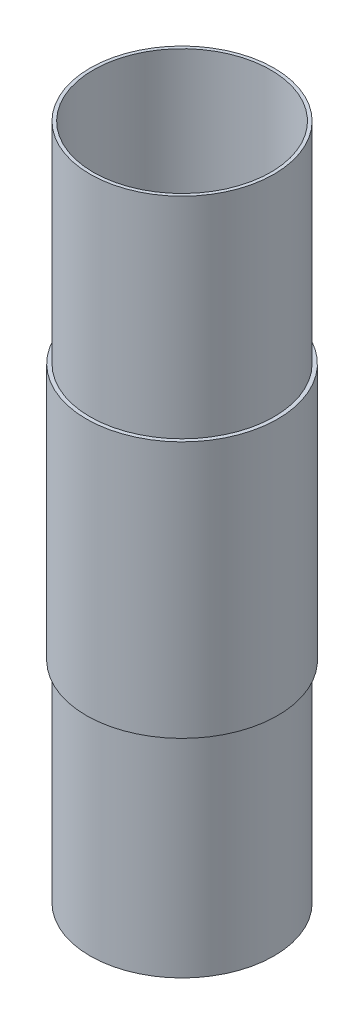
SolidWorks part; units mm, degrees
ref_plane "Front Plane" through (0, 0, 0) normal (0, 0, 1) x (1, 0, 0)
ref_plane "Top Plane" through (0, 0, 0) normal (0, 1, 0) x (1, 0, 0)
ref_plane "Right Plane" through (0, 0, 0) normal (1, 0, 0) x (0, 0, -1)
sketch "Sketch1" plane through (0, 0, 0) normal (0, 1, 0) x (1, 0, 0)
  circle A0 centre (0, 0) radius 41
  circle A1 centre (0, 0) radius 39.4
  circle A2 centre (0, 0) radius 38
  dimension "D1" = 82
  dimension "D2" = 78.8
  dimension "D3" = 76
extrude "Boss-Extrude1" add sketch "Sketch1" along normal mid plane 290 contours A1 A2 region at (-38.2856, 0, 0)
extrude "Boss-Extrude2" add sketch "Sketch1<3>" along normal mid plane 110 contours A0 A1 region at (-39.8403, 0, 0)
sketch "Sketch1<3>" plane through (0, 0, 0) normal (0, 1, 0) x (1, 0, 0) same geometry as "Sketch1"
